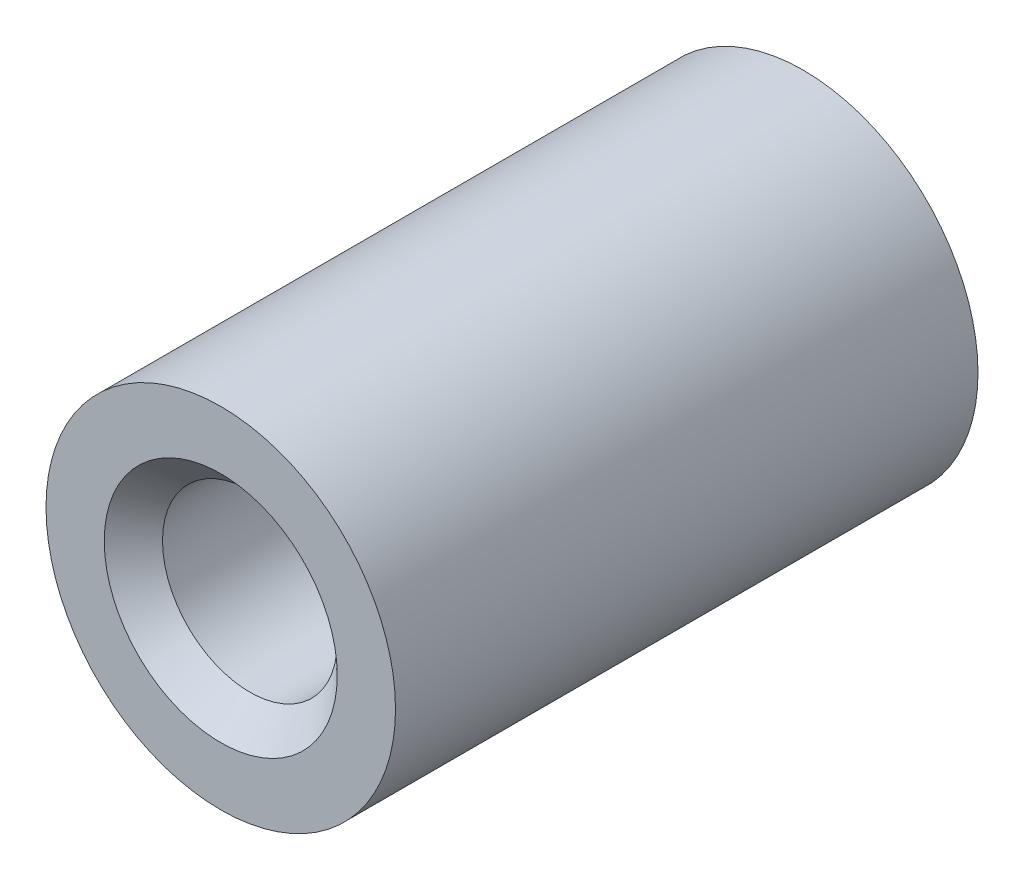
SolidWorks part; units mm, degrees
ref_plane "Piano frontale" through (0, 0, 0) normal (0, 0, 1) x (1, 0, 0)
ref_plane "Piano superiore" through (0, 0, 0) normal (0, 1, 0) x (1, 0, 0)
ref_plane "Piano destro" through (0, 0, 0) normal (1, 0, 0) x (0, 0, -1)
sketch "Schizzo1" plane through (0, 0, 0) normal (0, 0, 1) x (1, 0, 0)
  circle A0 centre (0, 0) radius 3
  circle A1 centre (0, 0) radius 1.5
  dimension "D1" = 3
  dimension "D2" = 6
extrude "Estrusione-Estrusione1" add sketch "Schizzo1" along normal blind 10
chamfer "Smusso1" distance 0.5 angle 45 1 edges at (1.5, 0, 10)
